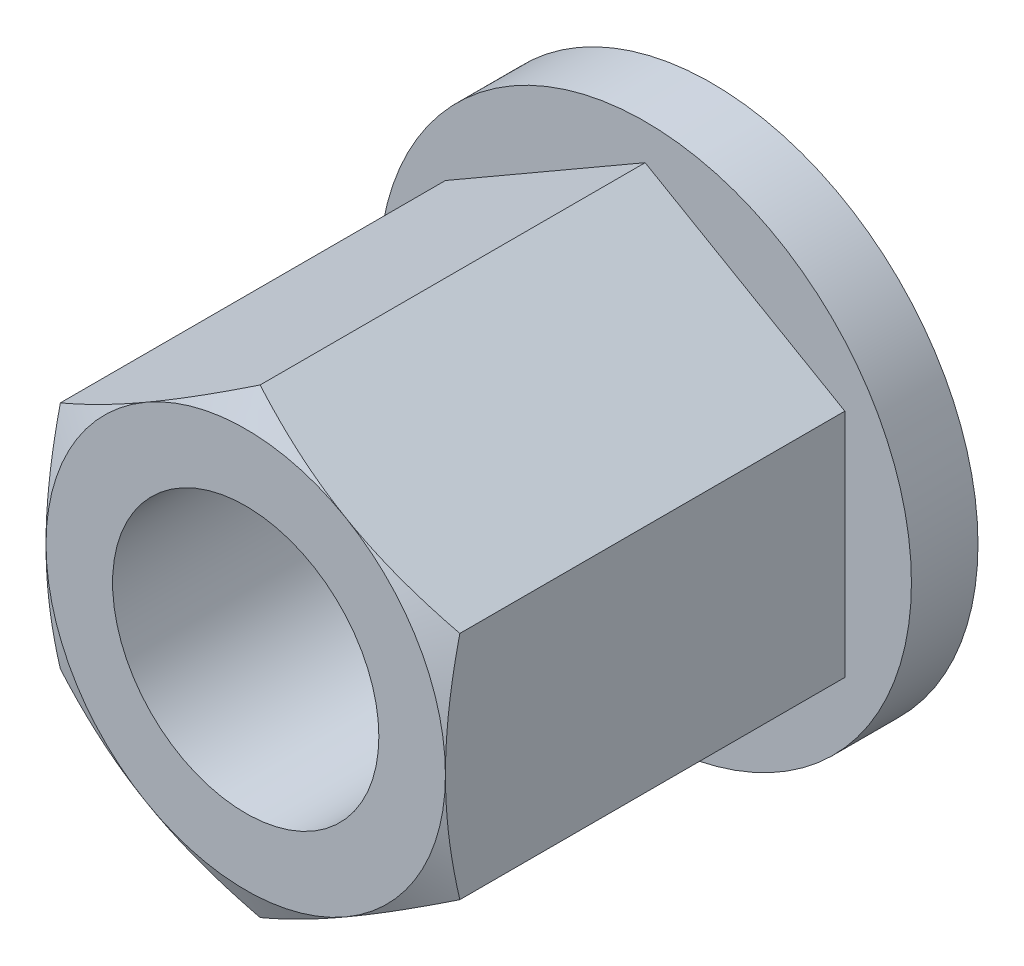
SolidWorks part; units mm, degrees
material "Fiberglass, FRP (Structural Grade)"
ref_plane "Front Plane" through (0, 0, 0) normal (0, 0, 1) x (1, 0, 0)
ref_plane "Top Plane" through (0, 0, 0) normal (0, 1, 0) x (1, 0, 0)
ref_plane "Right Plane" through (0, 0, 0) normal (1, 0, 0) x (0, 0, -1)
ref_axis "Axis1" through (0, 0, -18.9261) along (0, 0, 1)
ref_axis "Axis2" through (0, -19.1443, 0) along (0, 1, 0)
ref_axis "Axis3" through (-18.5295, 0, 0) along (1, 0, 0)
sketch "Sketch1" plane through (0, 0, 0) normal (1, 0, 0) x (0, 0, -1)
  line L0 (-34.5972, 0) -> (33.8471, 0) construction
  line L1 (-20.7445, 12.7) -> (0, 12.7)
  line L3 (-22.225, 6.35) -> (0, 6.35)
  line L4 (0, 12.7) -> (0, 6.35)
  line L7 (-22.225, 9.525) -> (-20.7445, 12.7)
  line L8 (-22.225, 9.525) -> (-22.225, 6.35)
  dimension "D1" = 25
  dimension "ID" = 12.7
  dimension "FLANGE DIA" = 25.4
  dimension "WIDTH" = 19.05
  dimension "O'ALL HEIGHT" = 22.225
revolve "Revolve1" add sketch "Sketch1" angle 360 about L0
sketch "Sketch2" plane through (0, 0, 0) normal (0, 0, 1) x (1, 0, 0)
  line L1 (9.525, -5.4993) -> (9.525, 5.4993)
  line L2 (9.525, 5.4993) -> (0, 10.9985)
  line L3 (0, 10.9985) -> (-9.525, 5.4993)
  line L4 (-9.525, 5.4993) -> (-9.525, -5.4993)
  line L5 (-9.525, -5.4993) -> (0, -10.9985)
  line L6 (0, -10.9985) -> (9.525, -5.4993)
  circle A0 centre (0, 0) radius 9.525 construction
  dimension "WIDTH" = 19.05
extrude "Cut-HEX" cut sketch "Sketch2" along normal through all from offset 3.175 flip side to cut
